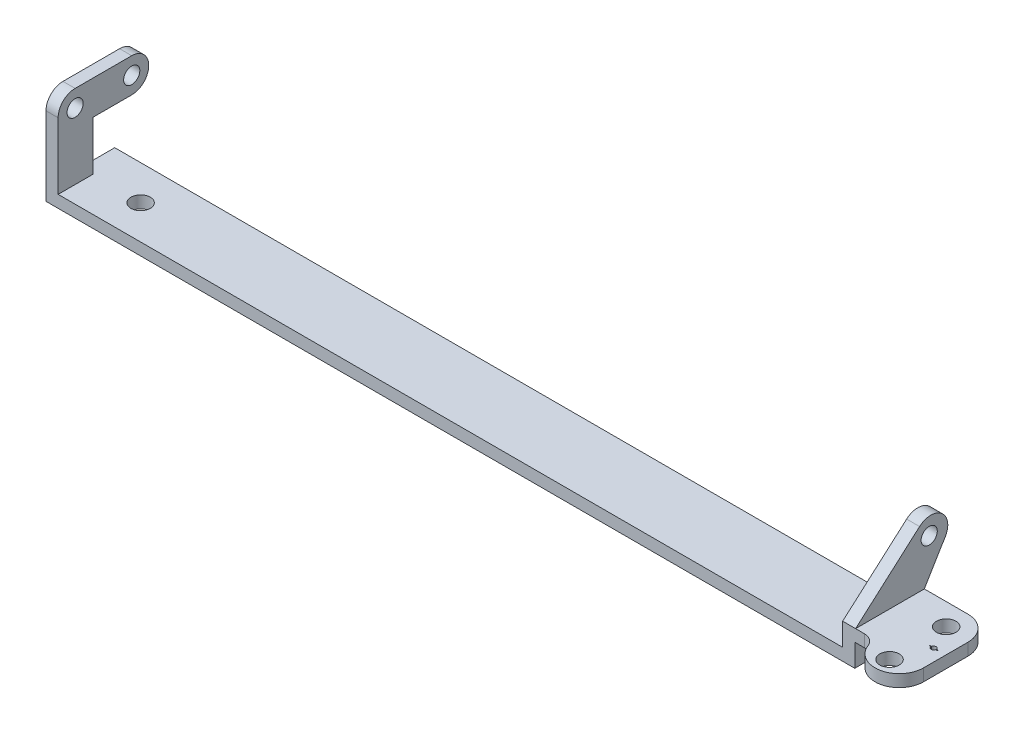
SolidWorks part; units mm, degrees
material "AISI 304"
ref_plane "Front Plane" through (0, 0, 0) normal (0, 0, 1) x (1, 0, 0)
ref_plane "Top Plane" through (0, 0, 0) normal (0, 1, 0) x (1, 0, 0)
ref_plane "Right Plane" through (0, 0, 0) normal (1, 0, 0) x (0, 0, -1)
sketch "Sketch1" plane through (0, 0, 0) normal (0, 0, 1) x (1, 0, 0)
  line L0 (0, 0) -> (1000, 0)
  line L1 (1000, 0) -> (1000, 28)
  line L2 (1000, 28) -> (1085, 28)
  dimension "D1" = 1000
  dimension "D2" = 28
  dimension "D3" = 85
extrude "Extrude-Thin1" add sketch "Sketch1" against normal blind 85 thin thin type one direction reverse wall 15
sketch "Sketch2" plane through (0, 0, 0) normal (-1, 0, 0) x (0, 0, 1)
  line L0 (0, 15) -> (0, 118)
  line L1 (0, 118) -> (-112, 118)
  line L2 (-112, 118) -> (-112, 76)
  line L3 (-112, 76) -> (-43, 76)
  line L4 (-43, 76) -> (-43, 15)
  line L5 (-85, 15) -> (0, 15) construction
  line L6 (-43, 15) -> (0, 15)
  line L7 (-85, 0) -> (-85, 15) construction
  line L8 (-112, 97) -> (-53.7993, 97) construction
  line L9 (-85, 15) -> (0, 15) construction
  dimension "D1" = 42
  dimension "D2" = 82
  dimension "D3" = 112
  dimension "D4" = 42
extrude "Boss-Extrude1" add sketch "Sketch2" against normal blind 15
sketch "Sketch3" plane through (985, 0, 0) normal (-1, 0, 0) x (0, 0, 1)
  line L0 (0, 43) -> (-79.1119, 112.7518)
  line L1 (-110.9908, 86.168) -> (-85, 43)
  line L2 (-85, 15) -> (0, 15) construction
  line L3 (-85, 15) -> (-85, 43) construction
  line L8 (0, 15) -> (0, 43)
  line L9 (0, 43) -> (-85, 43)
  line L10 (-85, 43) -> (-85, 15)
  line L11 (-85, 15) -> (0, 15)
  line L13 (0, 43) -> (-85, 43)
  arc A0 (-79.1119, 112.7518) -> (-110.9908, 86.168) centre (-93, 97) ccw
  dimension "D2" = 21
  dimension "D1" = 82
  dimension "D3" = 8
  dimension "D4" = 0
extrude "Boss-Extrude2" add sketch "Sketch3" against normal blind 16
fillet "Fillet1" radius 21 3 edges at (7.5, 76, -112) (7.5, 118, -112) (7.5, 118, 0)
sketch "Sketch5" plane through (0, 43, 0) normal (0, 1, 0) x (1, 0, 0)
  line L0 (1001, 0) -> (1085, 0) construction
  line L1 (1025, 0) -> (1085, 0)
  arc A0 (1085, 0) -> (1025, 0) centre (1055, 0) cw
  dimension "D1" = 30
extrude "Boss-Extrude3" add sketch "Sketch5" against normal up to surface (15 mm away) up to face at (1042.5, 28, -42.5)
fillet "Fillet2" radius 16 1 edges at (1025, 35.5, 0)
sketch "Sketch6" plane through (0, 43, 0) normal (0, 1, 0) x (1, 0, 0)
  line L0 (1001, 0) -> (1011.8723, 0) construction
  line L1 (985, 85) -> (985, 0) construction
  circle A0 centre (1055, -12) radius 12
  circle A1 centre (1055, 58) radius 12
  dimension "D2" = 24
  dimension "D1" = 70
  dimension "D3" = 58
  dimension "D4" = 70
extrude "Cut-Extrude2" cut sketch "Sketch6" against normal through all
fillet "Fillet3" radius 30 1 edges at (1085, 35.5, -85)
sketch "Sketch7" plane through (0, 15, 0) normal (0, 1, 0) x (1, 0, 0)
  line L0 (15, 0) -> (985, 0) construction
  circle A0 centre (75, 42) radius 12
  dimension "D1" = 75
  dimension "Hole_1" = 24
  dimension "D2" = 42
extrude "Cut-Extrude3" cut sketch "Sketch7" against normal through all
sketch "Sketch9" plane through (0, 0, 0) normal (-1, 0, 0) x (0, 0, 1)
  circle A0 centre (-91, 97) radius 10
  arc A1 (-112, 97) -> (-91, 76) centre (-91, 97) ccw construction
  circle A2 centre (-21, 97) radius 10
  dimension "D1" = 20
  dimension "D2" = 70
extrude "Cut-Extrude4" cut sketch "Sketch9" against normal through all
sketch "Sketch10" plane through (0, 43, 0) normal (0, 1, 0) x (1, 0, 0)
  line L0 (1085, 55) -> (1085, 0) construction
  line L1 (1070, 27.5) -> (1085, 27.5) construction
  line L3 (1075, 28) -> (1065, 28)
  line L4 (1075, 28) -> (1075, 27)
  line L5 (1075, 27) -> (1065, 27)
  line L6 (1065, 28) -> (1065, 27)
  line L7 (1075, 28) -> (1065, 27) construction
  line L8 (1075, 27) -> (1065, 28) construction
  circle A0 centre (1070, 27.5) radius 3
  dimension "D2" = 6
  dimension "D1" = 15
  dimension "D3" = 10
  dimension "D4" = 1
extrude "Cut-Extrude5" cut sketch "Sketch10" against normal through all contours L3 A0 | L5 A0 | A0 L5 L4 L3 | A0 L3 L6 L5 | L5 A0 L3 region at (1073.993, 43, -27.5) region at (1070, 43, -27.5) region at (1070, 43, -29.0474) region at (1066.007, 43, -27.5) region at (1070, 43, -25.9526)
